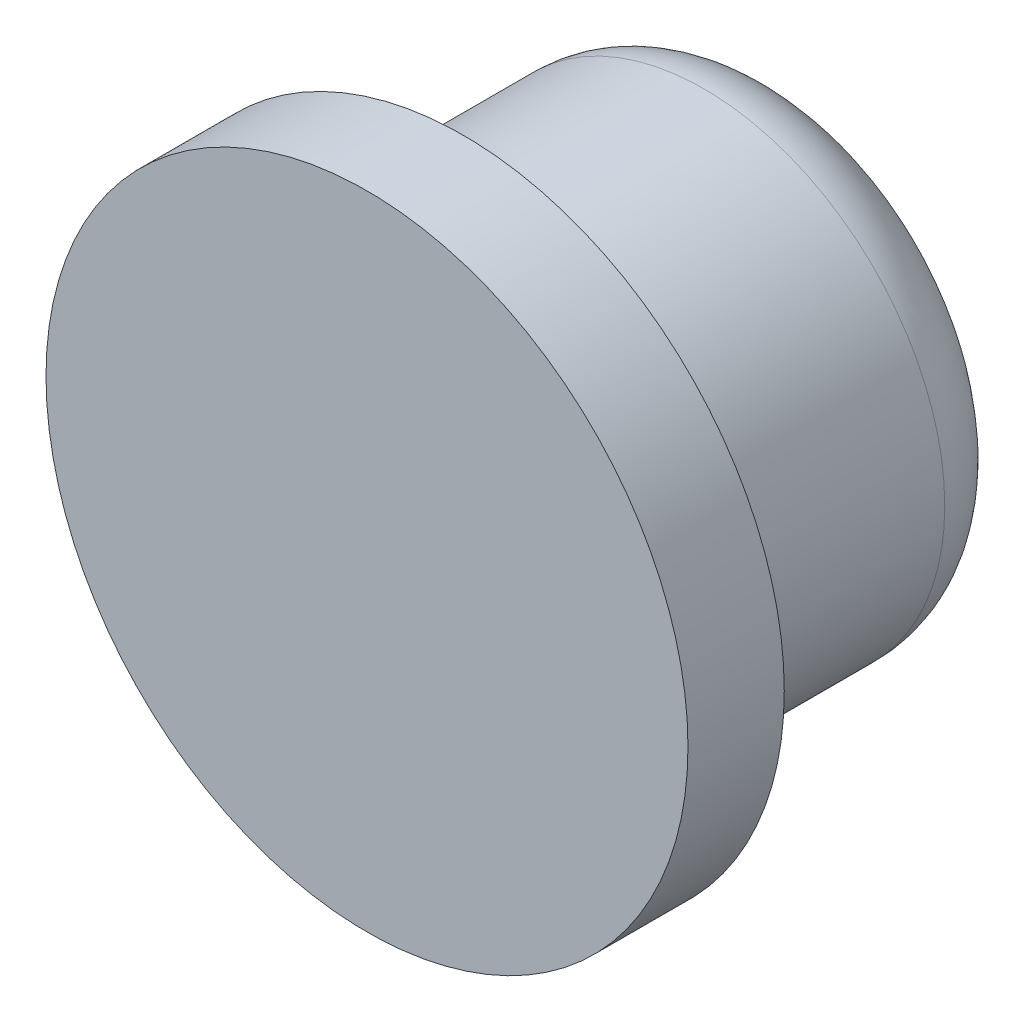
SolidWorks part; units mm, degrees
ref_plane "Front Plane" through (0, 0, 0) normal (0, 0, 1) x (1, 0, 0)
ref_plane "Top Plane" through (0, 0, 0) normal (0, 1, 0) x (1, 0, 0)
ref_plane "Right Plane" through (0, 0, 0) normal (1, 0, 0) x (0, 0, -1)
sketch "Sketch1" plane through (0, 0, 0) normal (0, 0, 1) x (1, 0, 0)
  circle A0 centre (-13.9898, 22.2675) radius 10
extrude "Boss-Extrude3" add sketch "Sketch1" along normal blind 3
sketch "Sketch3" plane through (0, 0, 0) normal (0, 0, -1) x (-1, 0, 0)
  line L0 (13.9898, 32.2675) -> (13.9898, 12.2675)
  circle A0 centre (13.9898, 22.2675) radius 10 construction
  circle A1 centre (13.9898, 22.2675) radius 7.5
extrude "Boss-Extrude4" add sketch "Sketch3" along normal blind 10 contours L0 A1 | L0 A1 region at (-17.1729, 22.2675, 0) region at (-10.8067, 22.2675, 0)
fillet "Fillet1" radius 2.5 1 edges at (-21.4898, 22.2675, -10)
